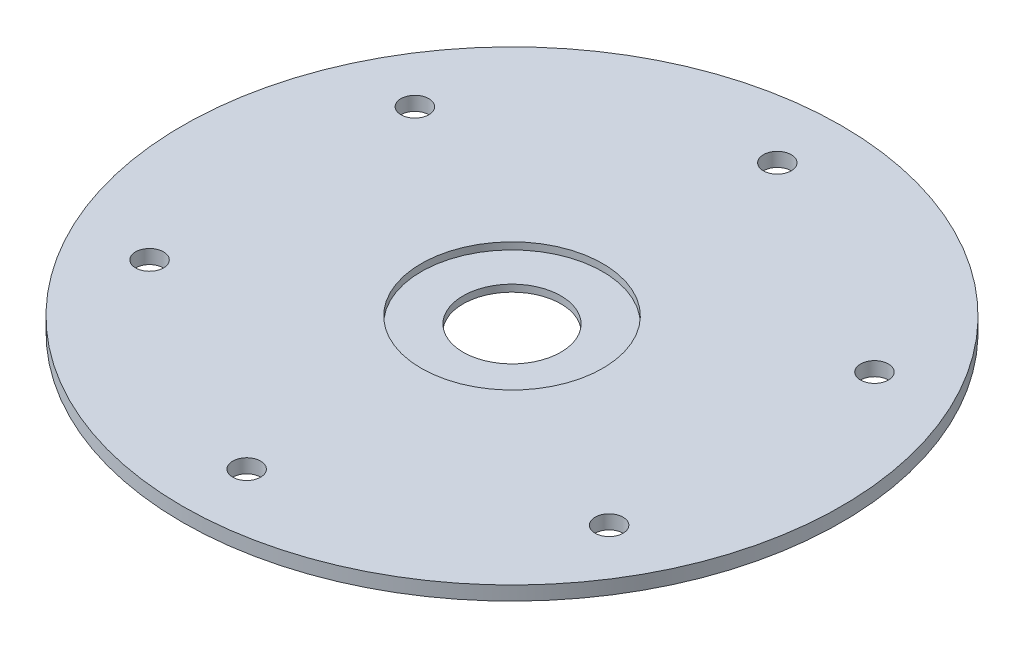
SolidWorks part; units mm, degrees
ref_plane "Front Plane" through (0, 0, 0) normal (0, 0, 1) x (1, 0, 0)
ref_plane "Top Plane" through (0, 0, 0) normal (0, 1, 0) x (1, 0, 0)
ref_plane "Right Plane" through (0, 0, 0) normal (1, 0, 0) x (0, 0, -1)
sketch "Sketch1" plane through (0, 0, 0) normal (0, 1, 0) x (1, 0, 0)
  circle A0 centre (0, 0) radius 47.2
  dimension "D1" = 94.4
extrude "Boss-Extrude1" add sketch "Sketch1" along normal blind 2
sketch "Sketch2" plane through (0, 2, 0) normal (0, 1, 0) x (1, 0, 0)
  circle A0 centre (0, 0) radius 13
  dimension "D1" = 26
extrude "Cut-Extrude1" cut sketch "Sketch2" against normal blind 1
sketch "Sketch3" plane through (0, 1, 0) normal (0, 1, 0) x (1, 0, 0)
  circle A0 centre (0, 0) radius 7
  dimension "D1" = 14
extrude "Cut-Extrude2" cut sketch "Sketch3" against normal through all
sketch "Sketch4" plane through (0, 2, 0) normal (0, 1, 0) x (1, 0, 0)
  line L0 (0, 50.52) -> (0, -52.0568) construction
  circle A0 centre (0, 38) radius 2
  dimension "D1" = 4
  dimension "D2" = 38
extrude "Cut-Extrude3" cut sketch "Sketch4" against normal through all
pattern_circular "CirPattern1" count 6 over 360 about axis through (0, 2, 0) along (0, 1, 0) of "Cut-Extrude3"
